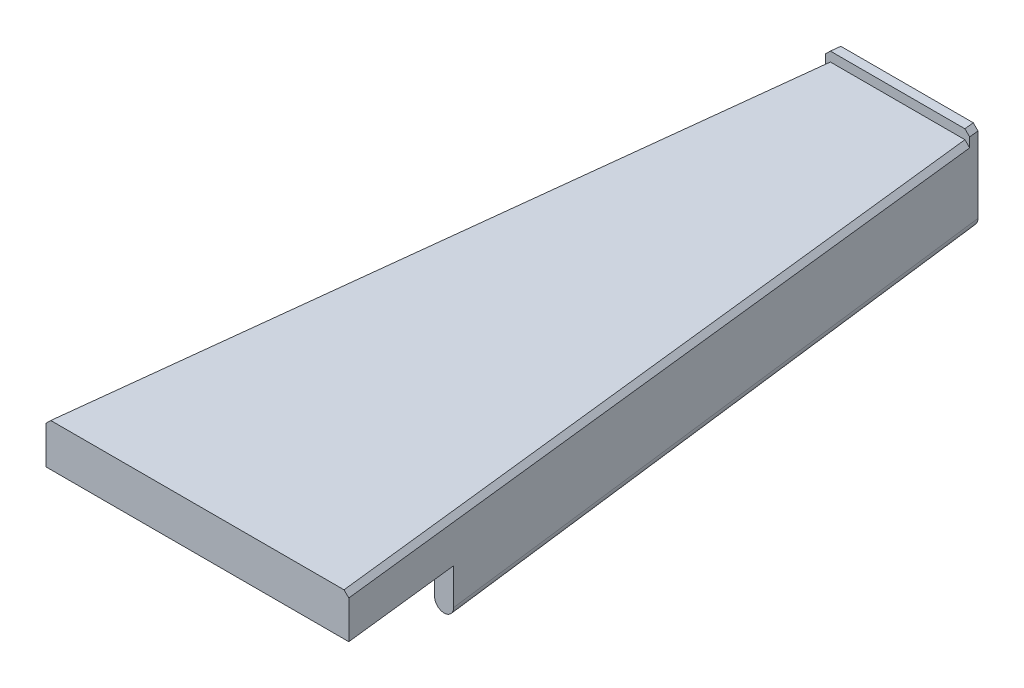
SolidWorks part; units mm, degrees
ref_plane "Front Plane" through (0, 0, 0) normal (0, 0, 1) x (1, 0, 0)
ref_plane "Top Plane" through (0, 0, 0) normal (0, 1, 0) x (1, 0, 0)
ref_plane "Right Plane" through (0, 0, 0) normal (1, 0, 0) x (0, 0, -1)
sketch "Sketch1" plane through (0, 0, 0) normal (0, 1, 0) x (1, 0, 0)
  line L0 (15, 0) -> (-15, 0)
  line L1 (0, 0) -> (0, -150) construction
  line L2 (32, -150) -> (-32, -150)
  line L3 (-32, -150) -> (-15, 0)
  line L4 (32, -150) -> (15, 0)
  dimension "\"neck length" = 150
extrude "Boss-Extrude1" add sketch "Sketch1" along normal blind 19
sketch "Sketch4" plane through (0, 0, 0) normal (1, 0, 0) x (0, 0, -1)
  line L0 (-150, 0) -> (0, 0)
  line L1 (0, 0) -> (0, 2)
  line L2 (0, 19) -> (0, 0) construction
  line L4 (0, 2) -> (-150, 0)
extrude "Cut-Extrude1" cut sketch "Sketch4" against normal through all both and the other way through all
shell "Shell1" thickness 4 removed face at (0, 1, 75)
fillet "Fillet2" 2 edges at (23.5, 1, 75) (19.4744, 1, 75) type full round first side face at (23.5, 10, 75) second side face at (19.4744, 5.5, 75) middle face at (0, 1, 75)
fillet "Fillet3" 2 edges at (-23.5, 1, 75) (-19.4744, 1, 75) type full round first side face at (-23.5, 10, 75) second side face at (-19.4744, 5.5, 75) middle face at (0.0015, 1, 75)
sketch "Sketch5" plane through (0, 19, 0) normal (0, 1, 0) x (1, 0, 0)
  line L0 (-15, 0) -> (-15.225, -1.9849)
  line L1 (-15, 0) -> (-32, -150) construction
  line L2 (-15.225, -1.9849) -> (15.225, -1.9849)
  line L3 (32, -150) -> (15, 0) construction
  line L4 (15.225, -1.9849) -> (15, 0)
  line L5 (15, 0) -> (-15, 0)
extrude "Boss-Extrude2" add sketch "Sketch5" along normal blind 2
chamfer "Chamfer1" distance 1 angle 45 2 edges at (23.6125, 19, 75.9925) (-23.6125, 19, 75.9925)
chamfer "Chamfer2" distance 1 angle 45 2 edges at (15.1125, 21, 0.9925) (-15.1125, 21, 0.9925)
sketch "Sketch6" plane through (0, 19, 0) normal (0, 1, 0) x (1, 0, 0)
  line L0 (-14.2186, -1.9849) -> (14.2186, -1.9849)
  line L1 (0, -1.9849) -> (0, -197.9912) construction
  line L2 (-36.3615, -197.3638) -> (36.3615, -197.3638)
  line L3 (30.9936, -150) -> (14.2186, -1.9849) construction
  line L4 (36.3615, -197.3638) -> (14.2186, -1.9849)
  line L5 (-14.2186, -1.9849) -> (-36.3615, -197.3638)
  line L6 (-14.2186, -1.9849) -> (-30.9936, -150) construction
extrude "Cut-Extrude2" [suppressed] cut sketch "Sketch6" against normal blind 1.6
sketch "Sketch7" plane through (0, 0, 150) normal (0, 0, 1) x (1, 0, 0)
  line L1 (-32, 9.9986) -> (32, 9.9986)
  line L2 (-32, 18) -> (-32, 1.9972) construction
  line L3 (32, 18) -> (32, 1.9972) construction
  line L4 (32, 9.9986) -> (32, 0)
  line L7 (-32, 0) -> (-32, 9.9986)
  line L8 (-32, 0) -> (32, 0)
extrude "Cut-Extrude3" cut sketch "Sketch7" against normal blind 25
equation "\"neck length\"= 200mm"
